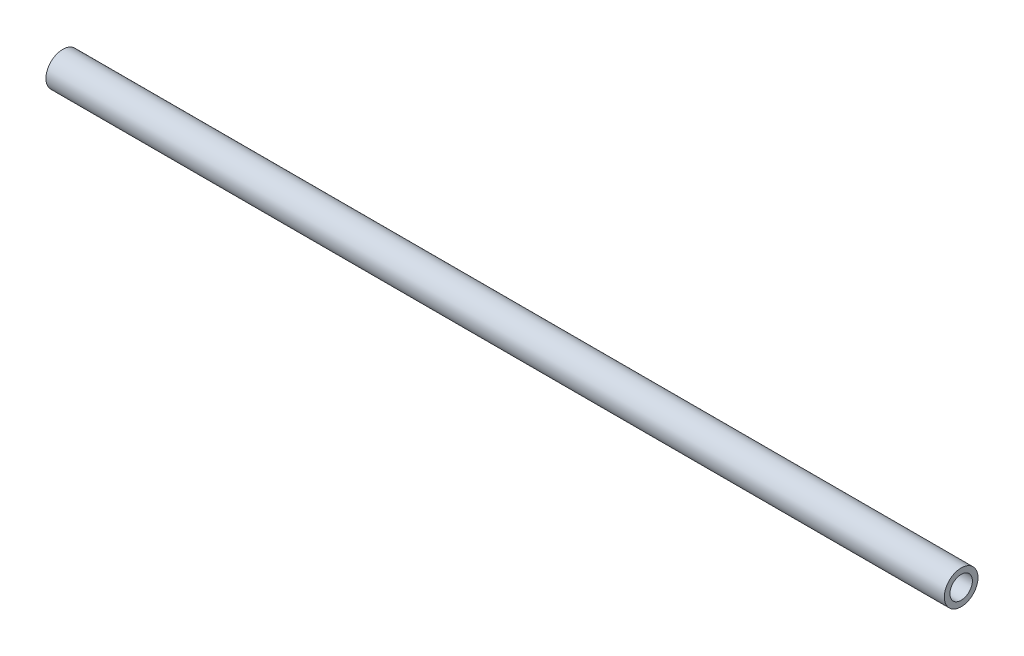
SolidWorks part; units mm, degrees
ref_plane "Front Plane" through (0, 0, 0) normal (0, 0, 1) x (1, 0, 0)
ref_plane "Top Plane" through (0, 0, 0) normal (0, 1, 0) x (1, 0, 0)
ref_plane "Right Plane" through (0, 0, 0) normal (1, 0, 0) x (0, 0, -1)
sketch "Sketch1" plane through (0, 0, 0) normal (1, 0, 0) x (0, 0, -1)
  circle A0 centre (0, 0) radius 6.35
  circle A1 centre (0, 0) radius 9.525
  dimension "D1" = 12.7
  dimension "D2" = 19.05
extrude "Boss-Extrude1" add sketch "Sketch1" along normal blind 508
